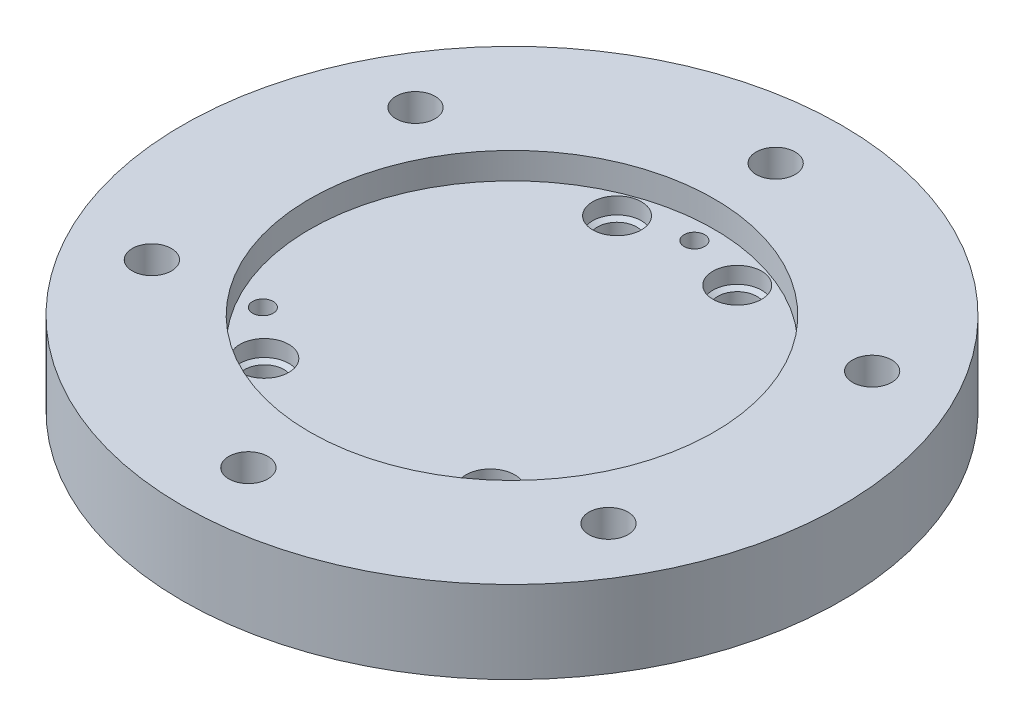
SolidWorks part; units mm, degrees
material "Copper"
ref_plane "Front Plane" through (0, 0, 0) normal (0, 0, 1) x (1, 0, 0)
ref_plane "Top Plane" through (0, 0, 0) normal (0, 1, 0) x (1, 0, 0)
ref_plane "Right Plane" through (0, 0, 0) normal (1, 0, 0) x (0, 0, -1)
ref_axis "Y Axis" through (0, 0.1588, 0) along (0, -1, 0)
sketch "outer" plane through (0, 0, 0) normal (0, 1, 0) x (1, 0, 0)
  circle A0 centre (0, 0) radius 19.05
  dimension "D1" = 38.1
extrude "Body" add sketch "outer" against normal blind 4.7625
sketch "inner" plane through (0, 0, 0) normal (0, 1, 0) x (1, 0, 0)
  circle A0 centre (0, 0) radius 11.684
  dimension "D1" = 23.368
extrude "Pocket" cut sketch "inner" against normal blind 1.524
sketch "Screw Position" plane through (0, 0, 0) normal (0, 1, 0) x (1, 0, 0)
  point P0 (0, -15.24)
  dimension "D1" = 15.24
hole_wizard "#4-40 Tapped Hole3" positions "Sketch12" profile "Sketch13" tap size "#4-40" standard "ANSI Inch" end condition through all
sketch "Sketch12" plane through (0, 0, 0) normal (0, 1, 0) x (1, 0, 0)
  point P0 (0, -15.24)
sketch "Sketch13" plane through (0, 0, 15.24) normal (1, 0, 0) x (0, 0, 1)
  line L0 (0, 0) -> (0, 4.7625)
  line L1 (0, 4.7625) -> (1.1303, 4.7625)
  line L2 (1.1303, 4.7625) -> (1.1303, 0)
  line L5 (1.1303, 0) -> (0, 0)
  line L11 (0, -6.35) -> (0, 107.95) construction
  dimension "Thru Tap Drill Dia." = 2.2606
  dimension "Thru Tap Drill Depth" = 4.7625
cosmetic thread "Hole Thread3" parameters "D2"=2.8448
pattern_circular "Screw Holes" count 6 over 360 about axis through (0, 0.1588, 0) along (0, -1, 0) of "#4-40 Tapped Hole3"
sketch "Inner Screw Position" plane through (0, 0, 0) normal (0, 1, 0) x (1, 0, 0)
  point P0 (0, 10.541)
  dimension "D1" = 10.541
hole_wizard "#0-80 Tapped Hole1" positions "Sketch16" profile "Sketch17" tap size "#0-80" standard "ANSI Inch" end condition through all
sketch "Sketch16" plane through (0, -1.524, 0) normal (0, 1, 0) x (1, 0, 0)
  point P0 (0, 10.541)
sketch "Sketch17" plane through (0, -1.524, -10.541) normal (1, 0, 0) x (0, 0, 1)
  line L0 (0, 0) -> (0, 3.2385)
  line L1 (0, 3.2385) -> (0.5956, 3.2385)
  line L2 (0.5956, 3.2385) -> (0.5956, 0)
  line L5 (0.5956, 0) -> (0, 0)
  line L11 (0, -6.35) -> (0, 107.95) construction
  dimension "Thru Tap Drill Dia." = 1.1913
  dimension "Thru Tap Drill Depth" = 3.2385
cosmetic thread "Hole Thread4" parameters "D2"=1.524
pattern_circular "Inner Screw Holes" count 3 over 360 about axis through (0, 0.1588, 0) along (0, -1, 0) of "#0-80 Tapped Hole1"
sketch "IO Postions" plane through (0, 0, 0) normal (0, 1, 0) x (1, 0, 0)
  line L0 (0, 0) -> (-3.4749, 9.5473) construction
  line L1 (0, 0) -> (-5.9719, 8.2196) construction
  point P0 (-3.4749, 9.5473)
  point P5 (-5.9719, 8.2196)
  point P6 (-8.0062, 6.2551)
  point P7 (-9.4202, 3.806)
  point P8 (-10.1043, 1.062)
  point P9 (-10.0056, -1.7643)
  point P13 (10.0056, -1.7643)
  point P14 (10.1043, 1.062)
  point P15 (9.4202, 3.806)
  point P16 (8.0062, 6.2551)
  point P17 (5.9719, 8.2196)
  point P18 (3.4749, 9.5473)
  point P19 (-6.5307, -7.783)
  point P20 (-4.1324, -9.2816)
  point P21 (-1.414, -10.0611)
  point P22 (1.414, -10.0611)
  point P23 (4.1324, -9.2816)
  point P24 (6.5307, -7.783)
  point P25 (0, 0)
  dimension "D3" = 16
  dimension "D2" = 6
  dimension "D4" = 3
hole_wizard "#43 (0.089) Diameter Hole1" positions "Sketch20" profile "Sketch21" hole size "#43" standard "ANSI Inch" end condition through all
sketch "Sketch20" plane through (0, -1.524, 0) normal (0, 1, 0) x (1, 0, 0)
  point P0 (-3.4749, 9.5473)
sketch "Sketch21" plane through (-3.4749, -1.524, -9.5473) normal (1, 0, 0) x (0, 0, 1)
  line L0 (0, 0) -> (0, 3.2385)
  line L1 (0, 3.2385) -> (1.1303, 3.2385)
  line L2 (1.1303, 3.2385) -> (1.1303, 0)
  line L5 (1.1303, 0) -> (0, 0)
  line L11 (0, -6.35) -> (0, 107.95) construction
  dimension "Thru Hole Dia." = 2.2606
  dimension "Thru Hole Depth" = 3.2385
hole_wizard "#34 (0.111) Diameter Hole1" positions "Sketch22" profile "Sketch23" hole size "#34" standard "ANSI Inch"
sketch "Sketch22" plane through (0, -1.524, 0) normal (0, 1, 0) x (1, 0, 0)
  point P0 (-3.4749, 9.5473)
sketch "Sketch23" plane through (-3.4749, -1.524, -9.5473) normal (1, 0, 0) x (0, 0, 1)
  line L0 (0, 0) -> (0, 1.7995)
  line L1 (0, 1.7995) -> (1.4097, 0.9525)
  line L2 (1.4097, 0.9525) -> (1.4097, 0)
  line L5 (1.4097, 0) -> (0, 0)
  line L10 (0, 1.7995) -> (-1.4097, 0.9525) construction
  line L11 (0, -6.35) -> (0, 107.95) construction
  dimension "Hole Dia." = 2.8194
  dimension "Hole Depth" = 0.9525
  dimension "Drill Angle" = 118
hole_wizard "#34 (0.111) Diameter Hole2" positions "Sketch28" profile "Sketch27" hole size "#34" standard "ANSI Inch"
sketch "Sketch28" plane through (0, -4.7625, 0) normal (0, -1, 0) x (-1, 0, 0)
  point P0 (3.4749, 9.5473)
sketch "Sketch27" plane through (-3.4749, -4.7625, -9.5473) normal (1, 0, 0) x (0, 0, -1)
  line L0 (0, 0) -> (0, 1.7995)
  line L1 (0, 1.7995) -> (1.4097, 0.9525)
  line L2 (1.4097, 0.9525) -> (1.4097, 0)
  line L5 (1.4097, 0) -> (0, 0)
  line L10 (0, 1.7995) -> (-1.4097, 0.9525) construction
  line L11 (0, -6.35) -> (0, 107.95) construction
  dimension "Hole Dia." = 2.8194
  dimension "Hole Depth" = 0.9525
  dimension "Drill Angle" = 118
sketch "IO Hole Position" plane through (0, 0, 0) normal (0, 1, 0) x (1, 0, 0)
  point P0 (3.4749, 9.5473)
  point P1 (-6.5307, -7.783)
  point P3 (6.5307, -7.783)
pattern_sketch "IO Holes Pattern" of "#43 (0.089) Diameter Hole1", "#34 (0.111) Diameter Hole1", "#34 (0.111) Diameter Hole2" driven by "IO Hole Position"
equation "\"outer_d\"= 3 / 2in"
equation "\"screw_r\"= 0.6in"
equation "\"inner_d\"= 0.920in"
equation "\"bottom_h\"= 3 / 16in"
equation "\"pocket_h\"= 0.060in"
equation "\"screw_inner_r\"= 0.415in"
equation "\"io_r\"= 0.4in"
equation "\"D1@outer\" = \"outer_d\""
equation "\"D1@Body\" = \"bottom_h\""
equation "\"D1@inner\" = \"inner_d\""
equation "\"D1@Pocket\"=\"pocket_h\""
equation "\"D1@Screw Position\" = \"screw_r\""
equation "\"D1@Inner Screw Position\" = \"screw_inner_r\""
equation "\"D1@IO Postions\" = \"io_r\""
